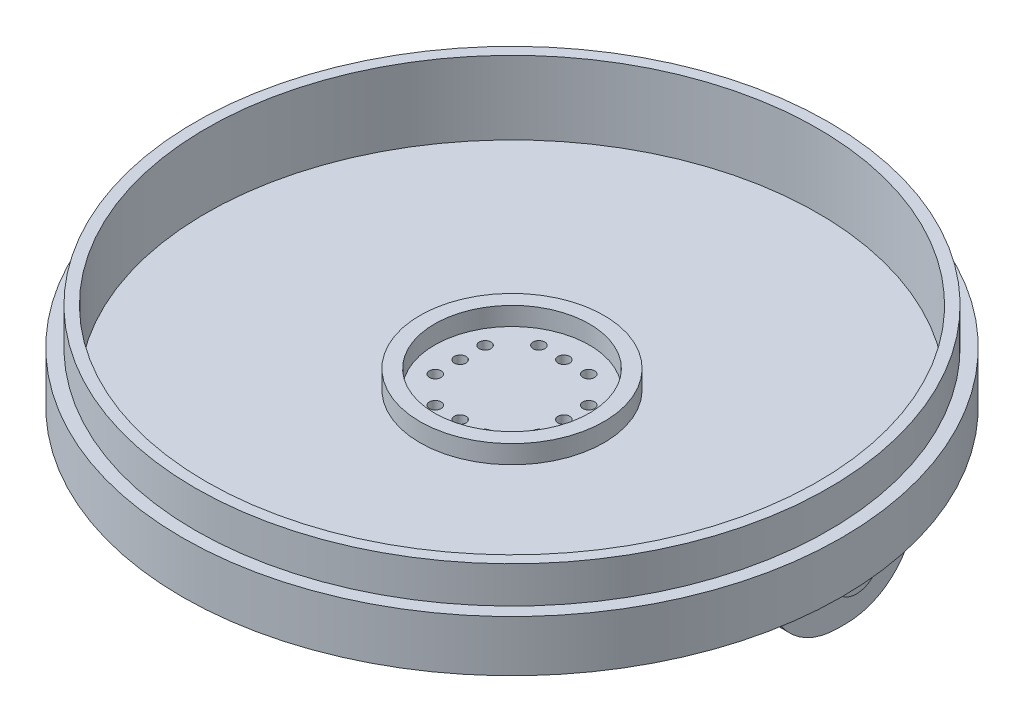
SolidWorks part; units mm, degrees
ref_plane "Alzado" through (0, 0, 0) normal (0, 0, 1) x (1, 0, 0)
ref_plane "Planta" through (0, 0, 0) normal (0, 1, 0) x (1, 0, 0)
ref_plane "Vista lateral" through (0, 0, 0) normal (1, 0, 0) x (0, 0, -1)
sketch "Croquis2" plane through (0, 0, 0) normal (0, 1, 0) x (1, 0, 0)
  circle A0 centre (0, 0) radius 45
  dimension "D1" = 90
extrude "Saliente-Extruir1" add sketch "Croquis2" along normal blind 2
sketch "Croquis3" plane through (0, 2, 0) normal (0, 1, 0) x (1, 0, 0)
  circle A1 centre (0, 0) radius 43.25
  circle A2 centre (0, 0) radius 41.75
  circle A3 centre (0, 0) radius 45 construction
  dimension "D1" = 1.75
  dimension "D2" = 1.5
extrude "Saliente-Extruir2" add sketch "Croquis3" along normal blind 10
sketch "Croquis4" plane through (0, 2, 0) normal (0, 1, 0) x (1, 0, 0)
  circle A1 centre (0, 0) radius 43.25 construction
  circle A2 centre (0, 0) radius 45
  circle A3 centre (0, 0) radius 45
  circle A4 centre (0, 0) radius 43.25
  dimension "D1" = 0
extrude "Saliente-Extruir3" add sketch "Croquis4" along normal blind 5
sketch "Croquis6" plane through (0, 2, 0) normal (0, 1, 0) x (1, 0, 0)
  circle A0 centre (0, 0) radius 10.56
  circle A1 centre (0, 0) radius 12.56
  dimension "D1" = 21.12
  dimension "D2" = 2
extrude "Saliente-Extruir4" add sketch "Croquis6" along normal blind 2.5
sketch "Croquis7" plane through (0, 2, 0) normal (0, 1, 0) x (1, 0, 0)
  line L0 (0, -49.8987) -> (0, 48.3647) construction
  circle A0 centre (0, 7.075) radius 0.8
  circle A1 centre (3.4, 7.075) radius 0.8
  circle A2 centre (-3.4, 7.075) radius 0.8
  circle A3 centre (7.075, 3.4) radius 0.8
  circle A4 centre (7.075, 0) radius 0.8
  circle A5 centre (7.075, -3.4) radius 0.8
  circle A6 centre (3.4, -7.075) radius 0.8
  circle A7 centre (0, -7.075) radius 0.8
  circle A8 centre (-3.4, -7.075) radius 0.8
  circle A9 centre (-7.075, -3.4) radius 0.8
  circle A10 centre (-7.075, 0) radius 0.8
  circle A11 centre (-7.075, 3.4) radius 0.8
  point P30 (0, 0)
  dimension "D2" = 1.6
  dimension "D3" = 3.4
  dimension "D4" = 1.6
  dimension "D1" = 7.075
  dimension "D5" = 4
extrude "Cortar-Extruir1" cut sketch "Croquis7" against normal through all
sketch "Croquis8" plane through (0, 0, 0) normal (0, -1, 0) x (1, 0, 0)
  line L0 (0, 47.342) -> (0, -48.0238) construction
  line L1 (8.25, 37.1867) -> (8.25, -17.101) construction
  line L2 (-11.7356, -29.1) -> (10.5982, -29.1) construction
  line L3 (-11.7356, -39.45) -> (10.5982, -39.45) construction
  line L4 (-7.25, 9.05) -> (14.75, 9.05)
  line L5 (23.75, 18.05) -> (-7.25, 18.05)
  line L6 (23.75, 18.05) -> (23.75, -39.45)
  line L7 (23.75, -39.45) -> (-7.25, -39.45)
  line L8 (-7.25, 18.05) -> (-7.25, 9.05)
  line L9 (23.75, 18.05) -> (-7.25, -39.45) construction
  line L10 (23.75, -39.45) -> (-7.25, 18.05) construction
  line L11 (14.75, 9.05) -> (14.75, -30.45)
  line L12 (-7.25, -30.45) -> (14.75, -30.45)
  line L13 (-7.25, -30.45) -> (-7.25, -39.45)
  point P9 (8.25, -10.7)
  dimension "D1" = 8.25
  dimension "D2" = 29.1
  dimension "D3" = 10.35
  dimension "D4" = 31
  dimension "D5" = 57.5
  dimension "D6" = 9
  dimension "D7" = 9
  dimension "D8" = 9
extrude "Saliente-Extruir5" add sketch "Croquis8" along normal blind 6
sketch "Croquis10" plane through (-7.25, 0, 0) normal (-1, 0, 0) x (0, 0, 1)
  line L0 (-10.7, -6) -> (-10.7, -26.5) construction
  line L1 (9.05, -6) -> (-30.45, -6) construction
  line L2 (30.1912, -16.25) -> (-51.5912, -16.25) construction
  line L3 (-30.45, -6) -> (-39.45, -6) construction
  line L5 (9.75, -24.7) -> (9.75, -6)
  line L7 (-31.15, -24.7) -> (-31.15, -6)
  line L8 (10.5512, -26.9016) -> (-31.15, -6) construction
  line L9 (9.75, -6) -> (-31.9512, -26.9016) construction
  line L10 (17.25, -21.25) -> (17.25, -6)
  line L11 (13.8, -24.7) -> (9.75, -24.7)
  line L12 (18.05, -6) -> (9.05, -6) construction
  line L13 (-35.2, -24.7) -> (-31.15, -24.7)
  line L14 (-38.65, -21.25) -> (-38.65, -6)
  line L15 (17.25, -6) -> (9.75, -6)
  line L16 (-31.15, -6) -> (-38.65, -6)
  circle A0 centre (-35.2, -21.25) radius 1.45
  circle A1 centre (-35.2, -11.25) radius 1.45
  circle A2 centre (13.8, -11.25) radius 1.45
  circle A3 centre (13.8, -21.25) radius 1.45
  arc A4 (17.25, -21.25) -> (13.8, -24.7) centre (13.8, -21.25) cw
  arc A6 (-38.65, -21.25) -> (-35.2, -24.7) centre (-35.2, -21.25) ccw
  circle A9 centre (13.8, -21.25) radius 3.45 construction
  circle A11 centre (-35.2, -21.25) radius 3.45 construction
  point P7 (-10.7, -16.25)
  point P15 (-10.7, -16.25)
  point P23 (17.1479, -13.25)
  point P24 (13.8, -13.25)
  point P25 (-31.8521, -23.25)
  point P27 (-31.8521, -13.25)
  point P28 (-35.2, -13.25)
  point P42 (17.1479, -23.25)
  dimension "D2" = 24.5
  dimension "D3" = 5
  dimension "D8" = 2.9
  dimension "D1" = 20.5
  dimension "D4" = 40.9
  dimension "D5" = 2
  dimension "D6" = 0
  dimension "D7" = 0
extrude "Saliente-Extruir6" add sketch "Croquis10" against normal blind 4
sketch "Croquis11" plane through (23.75, 0, 0) normal (1, 0, 0) x (0, 0, -1)
  line L0 (35.2, -24.7) -> (31.15, -24.7) construction
  line L1 (31.15, -6) -> (11.45, -6)
  line L2 (31.15, -6) -> (31.15, -24.7)
  line L3 (31.15, -24.7) -> (11.45, -24.7)
  line L4 (11.45, -6) -> (11.45, -24.7)
  dimension "D1" = 0
  dimension "D2" = 19.7
extrude "Saliente-Extruir7" add sketch "Croquis11" against normal blind 2
sketch "Croquis12" plane through (23.75, 0, 0) normal (1, 0, 0) x (0, 0, -1)
  line L0 (35.2, -11.25) -> (35.2, -21.25) construction
  line L1 (35.2, -16.25) -> (9.8958, -16.25) construction
  line L2 (31.15, -24.7) -> (31.15, -6) construction
  circle A0 centre (20.77, -16.25) radius 3.1519
  dimension "D1" = 10.38
extrude "Saliente-Extruir8" add sketch "Croquis12" along normal blind 2.5
fillet "Redondeo1" radius 9.25 4 edges at (22.75, -24.7, -31.15) (22.75, -24.7, -11.45) (22.75, -6, -11.45) (22.75, -6, -31.15)
fillet "Redondeo2" radius 0.7 6 edges at (-3.25, -6, -34.9) (-3.25, -6, 13.5) (-5.25, -6, 9.75) (-5.25, -6, 17.25) (-5.25, -6, -31.15) (-5.25, -6, -38.65)
fillet "Redondeo4" radius 5 1 edges at (23.75, -3, -39.45)
